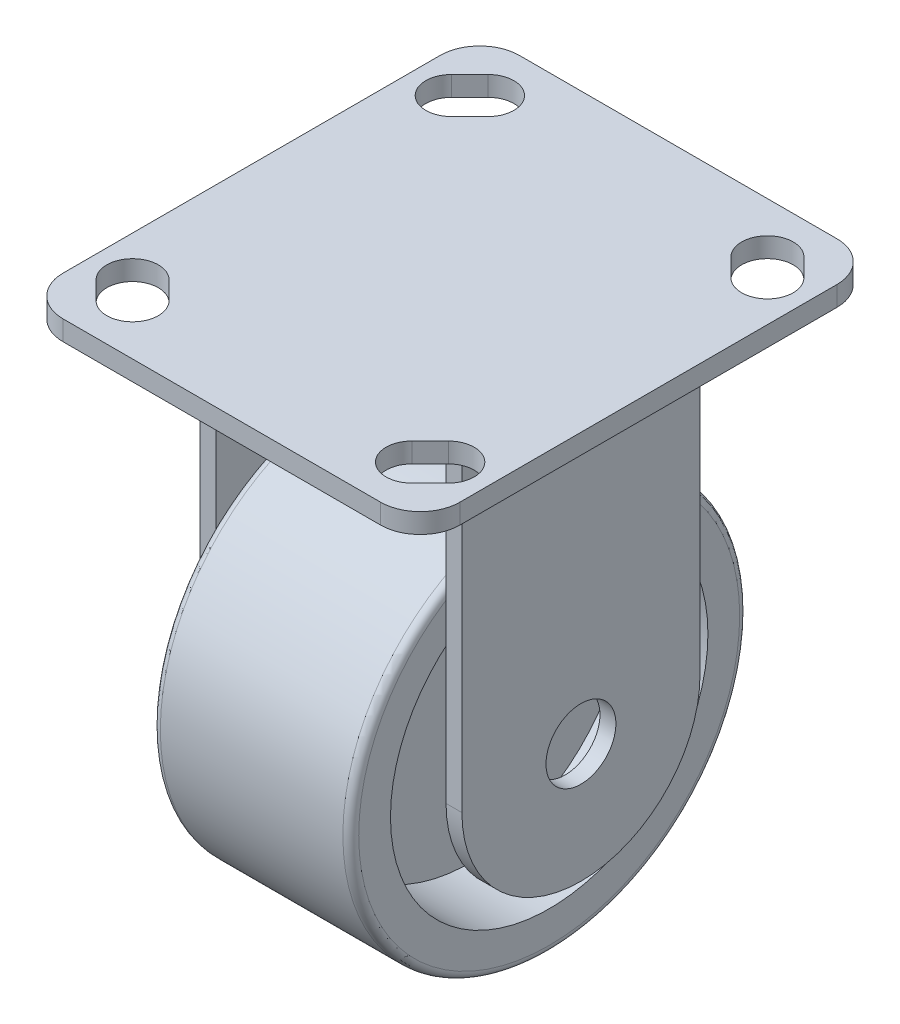
SolidWorks part; units mm, degrees
ref_plane "Front Plane" through (0, 0, 0) normal (0, 0, 1) x (1, 0, 0)
ref_plane "Top Plane" through (0, 0, 0) normal (0, 1, 0) x (1, 0, 0)
ref_plane "Right Plane" through (0, 0, 0) normal (1, 0, 0) x (0, 0, -1)
sketch "Sketch1" plane through (0, 0, 0) normal (1, 0, 0) x (0, 0, -1)
  circle A0 centre (0, 0) radius 50
  circle A1 centre (0, 0) radius 5
  dimension "D1" = 100
  dimension "D2" = 10
extrude "Boss-Extrude1" add sketch "Sketch1" along normal mid plane 50
sketch "Sketch3" plane through (0, 0, 0) normal (1, 0, 0) x (0, 0, -1)
  circle A0 centre (0, 0) radius 40
  dimension "D1" = 80
extrude "Cut-Extrude1" cut sketch "Sketch3" against normal blind 20 from offset 5 offset against normal yes
extrude "Cut-Extrude2" cut sketch "Sketch3<2>" along normal blind 20 from offset 5
sketch "Sketch3<2>" plane through (0, 0, 0) normal (1, 0, 0) x (0, 0, -1) same geometry as "Sketch3"
ref_plane "Plane1" through (-29, 0, 0) normal (-1, 0, 0) x (0, 0, 1)
sketch "Sketch4" plane through (-29, 0, 0) normal (-1, 0, 0) x (0, 0, 1)
  line L0 (0, 0) -> (0, 80) construction
  line L1 (-30, 0) -> (-30, 80)
  line L2 (30, 0) -> (30, 80)
  line L3 (-30, 80) -> (30, 80)
  arc A0 (-30, 0) -> (30, 0) centre (0, 0) ccw
  arc A1 (30, 80) -> (-30, 80) centre (0, 80) ccw construction
  circle A2 centre (0, 0) radius 50 construction
  circle A3 centre (0, 0) radius 8.8042
  point P3 (0, 52.7688)
  point P8 (0, -50)
  dimension "D1" = 30
  dimension "D2" = 130
extrude "Boss-Extrude2" add sketch "Sketch4" along normal blind 4 separate body
mirror "Mirror4" about plane through (0, 0, 0) normal (1, 0, 0) of bodies 104
sketch "Sketch5" plane through (0, 80, 0) normal (0, 1, 0) x (1, 0, 0)
  line L0 (35.2019, 44.7981) -> (39.7981, 40.2019) construction
  line L1 (-50, 57.5) -> (50, 57.5)
  line L2 (-50, 57.5) -> (-50, -57.5)
  line L3 (-50, -57.5) -> (50, -57.5)
  line L4 (50, 57.5) -> (50, -57.5)
  line L5 (0, -57.5) -> (0, 57.5) construction
  line L6 (-50, 0) -> (50, 0) construction
  line L7 (-37.5, 42.5) -> (37.5, 42.5) construction
  line L8 (-37.5, 42.5) -> (-37.5, -42.5) construction
  line L9 (-37.5, -42.5) -> (37.5, -42.5) construction
  line L10 (37.5, 42.5) -> (37.5, -42.5) construction
  line L11 (0, -42.5) -> (0, 42.5) construction
  line L12 (-37.5, 0) -> (37.5, 0) construction
  line L13 (39.7981, 49.3943) -> (44.3943, 44.7981)
  line L14 (30.6057, 40.2019) -> (35.2019, 35.6057)
  line L15 (-39.7981, 40.2019) -> (-35.2019, 44.7981) construction
  line L16 (-44.3943, 44.7981) -> (-39.7981, 49.3943)
  line L17 (-35.2019, 35.6057) -> (-30.6057, 40.2019)
  line L18 (-39.7981, -40.2019) -> (-35.2019, -44.7981) construction
  line L19 (-35.2019, -35.6057) -> (-30.6057, -40.2019)
  line L20 (-44.3943, -44.7981) -> (-39.7981, -49.3943)
  line L21 (39.7981, -40.2019) -> (35.2019, -44.7981) construction
  line L22 (44.3943, -44.7981) -> (39.7981, -49.3943)
  line L23 (35.2019, -35.6057) -> (30.6057, -40.2019)
  arc A0 (39.7981, 49.3943) -> (30.6057, 40.2019) centre (35.2019, 44.7981) ccw
  arc A1 (35.2019, 35.6057) -> (44.3943, 44.7981) centre (39.7981, 40.2019) ccw
  arc A2 (-44.3943, 44.7981) -> (-35.2019, 35.6057) centre (-39.7981, 40.2019) ccw
  arc A3 (-30.6057, 40.2019) -> (-39.7981, 49.3943) centre (-35.2019, 44.7981) ccw
  arc A4 (-35.2019, -35.6057) -> (-44.3943, -44.7981) centre (-39.7981, -40.2019) ccw
  arc A5 (-39.7981, -49.3943) -> (-30.6057, -40.2019) centre (-35.2019, -44.7981) ccw
  arc A6 (44.3943, -44.7981) -> (35.2019, -35.6057) centre (39.7981, -40.2019) ccw
  arc A7 (30.6057, -40.2019) -> (39.7981, -49.3943) centre (35.2019, -44.7981) ccw
  point P0 (0, 0)
  point P4 (0, 0)
  point P13 (37.5, 42.5)
  point P23 (-37.5, 42.5)
  point P29 (-37.5, -42.5)
  point P36 (37.5, -42.5)
  dimension "D5" = 6.5
  dimension "D1" = 115
  dimension "D2" = 100
  dimension "D3" = 75
  dimension "D4" = 85
  dimension "D6" = 6.5
  dimension "D7" = 45
  dimension "D8" = 45
  dimension "D9" = 45
  dimension "D10" = 45
extrude "Boss-Extrude3" add sketch "Sketch5" along normal blind 5
fillet "Fillet1" radius 10 4 edges at (50, 82.5, -57.5) (-50, 82.5, -57.5) (50, 82.5, 57.5) (-50, 82.5, 57.5)
fillet "Fillet2" radius 2 2 edges at (-25, 0, -50) (25, 0, -50)
